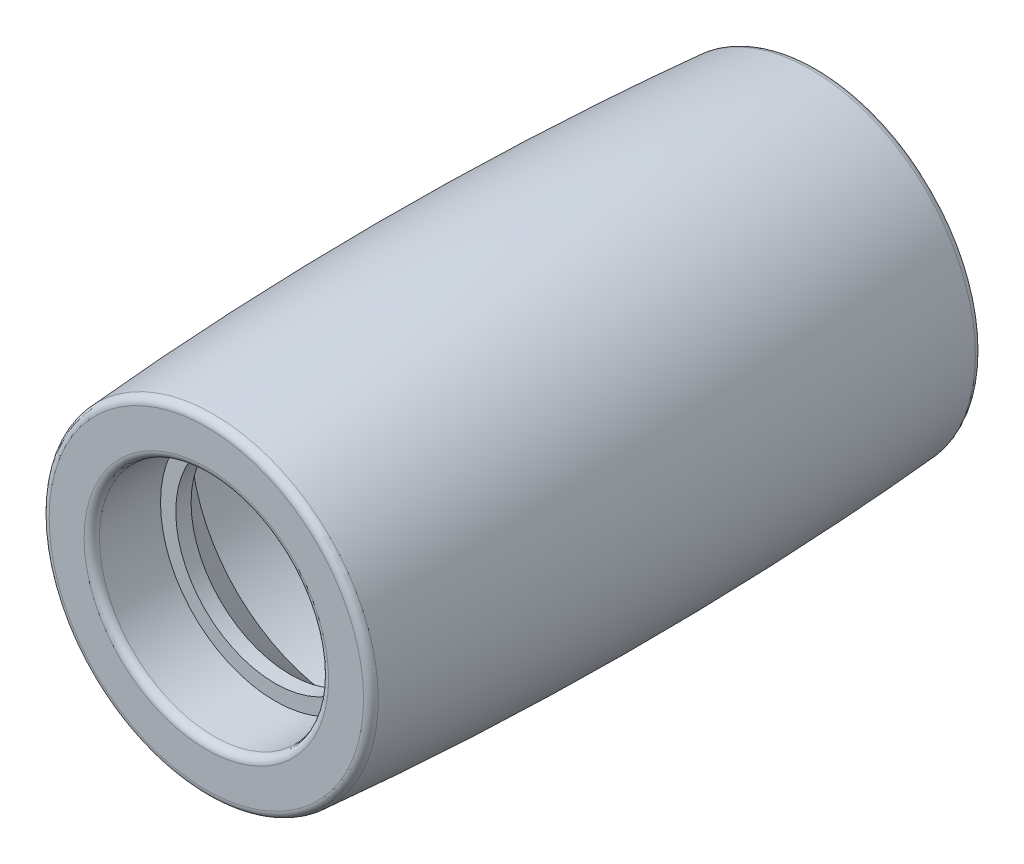
SolidWorks part; units mm, degrees
ref_plane "Ebene vorne" through (0, 0, 0) normal (0, 0, 1) x (1, 0, 0)
ref_plane "Ebene oben" through (0, 0, 0) normal (0, 1, 0) x (1, 0, 0)
ref_plane "Ebene rechts" through (0, 0, 0) normal (1, 0, 0) x (0, 0, -1)
sketch "Skizze1" plane through (450, 0, 0) normal (1, 0, 0) x (0, 0, -1)
  line L7 (21, 20.2121) -> (50, 20.2121) construction
  line L16 (50, 23) -> (50, 20.2121) construction
  line L17 (10, 21.5) -> (10, 15) construction
  line L18 (19, 15) -> (10, 15) construction
  line L19 (19, 15) -> (19, 5) construction
  line L20 (19, 13) -> (21, 13) construction
  line L21 (21, 13) -> (28.2121, 20.2121) construction
  line L22 (0, 0) -> (100, 0) construction
  line L23 (28.2121, 20.2121) -> (50, 20.2121)
  line L24 (50, 23) -> (50, 20.2121)
  line L25 (10, 21.5) -> (10, 15)
  line L26 (19, 15) -> (10, 15)
  line L27 (19, 15) -> (19, 13)
  line L28 (19, 13) -> (21, 13)
  line L29 (21, 13) -> (28.2121, 20.2121)
  line L30 (0, 0) -> (100, 0) construction
  arc A2 (90, 21.5) -> (10, 21.5) centre (50, -511.0833) ccw construction
  arc A3 (50, 23) -> (10, 21.5) centre (50, -511.0833) ccw
revolve "Rotation1" add sketch "Skizze1" angle 360 about L30
mirror "Spiegeln1" about plane through (450, 23, -50) normal (0, 0, 1) of bodies 101
fillet "Verrundung1" radius 1 4 edges at (471.5, 0, -10) (465, 0, -10) (471.5, 0, -90) (465, 0, -90)
